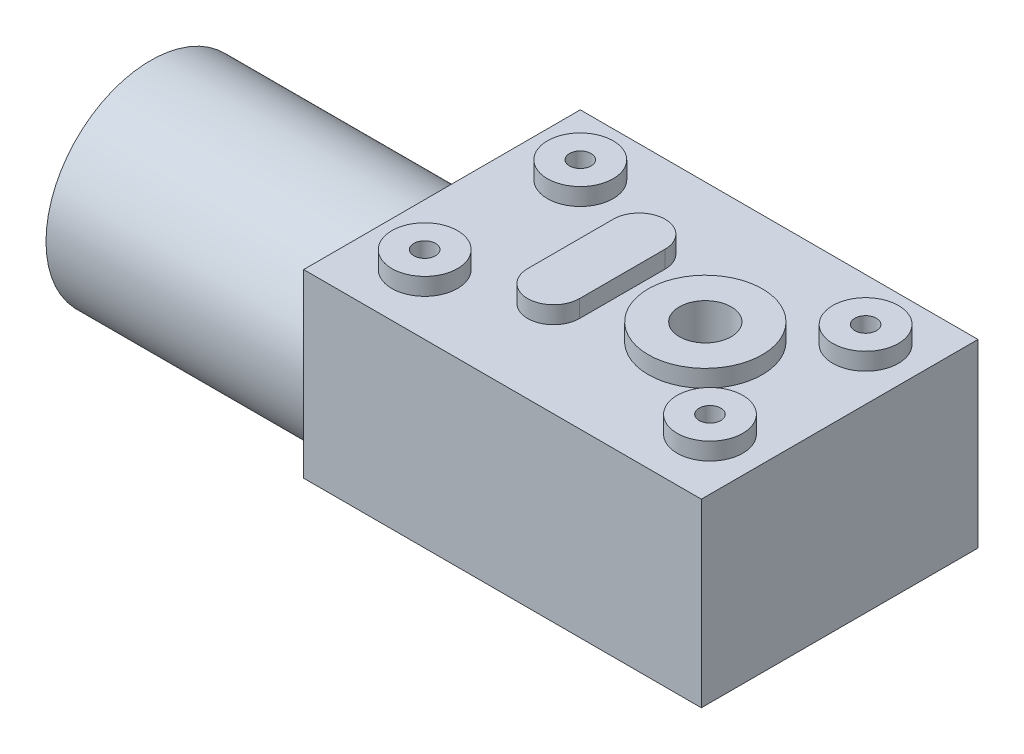
SolidWorks part; units mm, degrees
ref_plane "Front Plane" through (0, 0, 0) normal (0, 0, 1) x (1, 0, 0)
ref_plane "Top Plane" through (0, 0, 0) normal (0, 1, 0) x (1, 0, 0)
ref_plane "Right Plane" through (0, 0, 0) normal (1, 0, 0) x (0, 0, -1)
sketch "Sketch1" plane through (0, 0, 0) normal (0, 1, 0) x (1, 0, 0)
  line L1 (-23, -16) -> (23, -16)
  line L2 (-23, -16) -> (-23, 16)
  line L3 (-23, 16) -> (23, 16)
  line L4 (23, -16) -> (23, 16)
  line L5 (-23, -16) -> (23, 16) construction
  line L6 (-23, 16) -> (23, -16) construction
  line L7 (-16.5394, 9.0215) -> (16.4606, 9.0215)
  line L8 (-16.5394, 9.0215) -> (-16.5394, -8.9785)
  line L9 (-16.5394, -8.9785) -> (16.4606, -8.9785)
  line L10 (16.4606, 9.0215) -> (16.4606, -8.9785)
  circle A0 centre (7.4606, 0) radius 3
  point P1 (0, 0)
  dimension "D3" = 33
  dimension "D8" = 6
  dimension "D1" = 32
  dimension "D2" = 46
  dimension "D4" = 18
  dimension "D5" = 9
extrude "Boss-Extrude1" add sketch "Sketch1" along normal blind 22.3 contours L2 | L1 L4 L3 L2 L7 L10 L9 L8 | L10 L7 L8 L9 A0 region at (-22.4396, 0, 0) region at (-0.4142, 0, -0.0226)
sketch "Sketch3" plane through (0, 22.3, 0) normal (0, 1, 0) x (1, 0, 0)
  line L0 (-23, -16) -> (-23, 16) construction
  line L1 (-16, -9) -> (17, -9) construction
  line L2 (-16, -9) -> (-16, 9) construction
  line L3 (-16, 9) -> (17, 9) construction
  line L4 (17, -9) -> (17, 9) construction
  line L5 (-23, 16) -> (23, 16) construction
  line L6 (-5.1394, -4.95) -> (-5.1394, 4.95) construction
  line L7 (-8.1394, -4.95) -> (-8.1394, 4.95)
  line L8 (-2.1394, -4.95) -> (-2.1394, 4.95)
  line L9 (23, 0) -> (-23, 0) construction
  line L10 (23, -16) -> (23, 16) construction
  line L11 (-2.1394, 0) -> (0.8606, 0) construction
  line L12 (-16, -9) -> (17, -9) construction
  circle A0 centre (-16, -9) radius 3.8
  circle A4 centre (7.4606, 0) radius 6.6
  arc A5 (-8.1394, -4.95) -> (-2.1394, -4.95) centre (-5.1394, -4.95) ccw
  arc A6 (-2.1394, 4.95) -> (-8.1394, 4.95) centre (-5.1394, 4.95) ccw
  circle A7 centre (17, -9) radius 3.8
  circle A8 centre (17, 9) radius 3.8
  circle A9 centre (-16, 9) radius 3.8
  point P17 (-5.1394, 0)
  dimension "D5" = 7.6
  dimension "D6" = 13.2
  dimension "D1" = 33
  dimension "D2" = 18
  dimension "D3" = 7
  dimension "D4" = 7
  dimension "D7" = 6
  dimension "D8" = 9.9
  dimension "D9" = 3
  dimension "D12" = 33
  dimension "D10" = 2
  dimension "D11" = 2
extrude "Boss-Extrude3" add sketch "Sketch3" along normal blind 2
sketch "Sketch2" plane through (-23, 0, 0) normal (-1, 0, 0) x (0, 0, 1)
  line L0 (2.9, 21.3) -> (2.9, 22.3) construction
  line L1 (16, 22.3) -> (-16, 22.3) construction
  line L2 (15, 9.2) -> (16, 9.2) construction
  line L3 (16, 22.3) -> (16, 0) construction
  circle A0 centre (2.9, 9.2) radius 12.1
  dimension "D1" = 24.2
  dimension "D2" = 1
  dimension "D3" = 1
sketch "Sketch4" plane through (0, 22.3, 0) normal (0, -1, 0) x (1, 0, 0)
  circle A0 centre (7.4606, 0) radius 3 construction
  circle A1 centre (7.4606, 0) radius 3
extrude "Cut-Extrude1" cut sketch "Sketch4" against normal through all
extrude "Boss-Extrude2" add sketch "Sketch2" along normal blind 30.8
chamfer "Chamfer1" distance 1.4 angle 75 3 edges at (0, 0, 16) (23, 0, 0) (0, 0, -16) first distance on face at (0, 11.15, 16) first distance on face at (23, 11.15, 0) first distance on face at (0, 11.15, -16)
hole_wizard "Tap Drill for M3x0.5 Tap1" positions "Sketch5" profile "Sketch6" hole size "M3x0.5" standard "ANSI Metric"
sketch "Sketch5" plane through (0, 24.3, 0) normal (0, 1, 0) x (1, 0, 0)
  point P0 (-16, -9)
  point P17 (-16, 9)
  point P20 (17, 9)
  point P23 (17, -9)
  point P26 (17, -9)
sketch "Sketch6" plane through (-16, 24.3, 9) normal (1, 0, 0) x (0, 0, 1)
  line L0 (0, 0) -> (0, 3.3511)
  line L1 (0, 3.3511) -> (1.25, 2.6)
  line L2 (1.25, 2.6) -> (1.25, 0)
  line L5 (1.25, 0) -> (0, 0)
  line L10 (0, 3.3511) -> (-1.25, 2.6) construction
  line L11 (0, -6.35) -> (0, 107.95) construction
  dimension "Hole Dia." = 2.5
  dimension "Hole Depth" = 2.6
  dimension "Drill Angle" = 118
sketch "Sketch8" plane through (-53.8, 0, 0) normal (-1, 0, 0) x (0, 0, 1)
  circle A3 centre (2.9, 9.2) radius 11.8
  circle A4 centre (2.9, 9.2) radius 11.8
  dimension "D1" = 0.3
extrude "Cut-Extrude2" cut sketch "Sketch8" against normal blind 0.8
sketch "Sketch7" plane through (-53, 0, 0) normal (-1, 0, 0) x (0, 0, 1)
  circle A0 centre (2.9, 9.2) radius 3.2
  dimension "D1" = 6.4
extrude "Boss-Extrude5" add sketch "Sketch7" along normal blind 2.7
